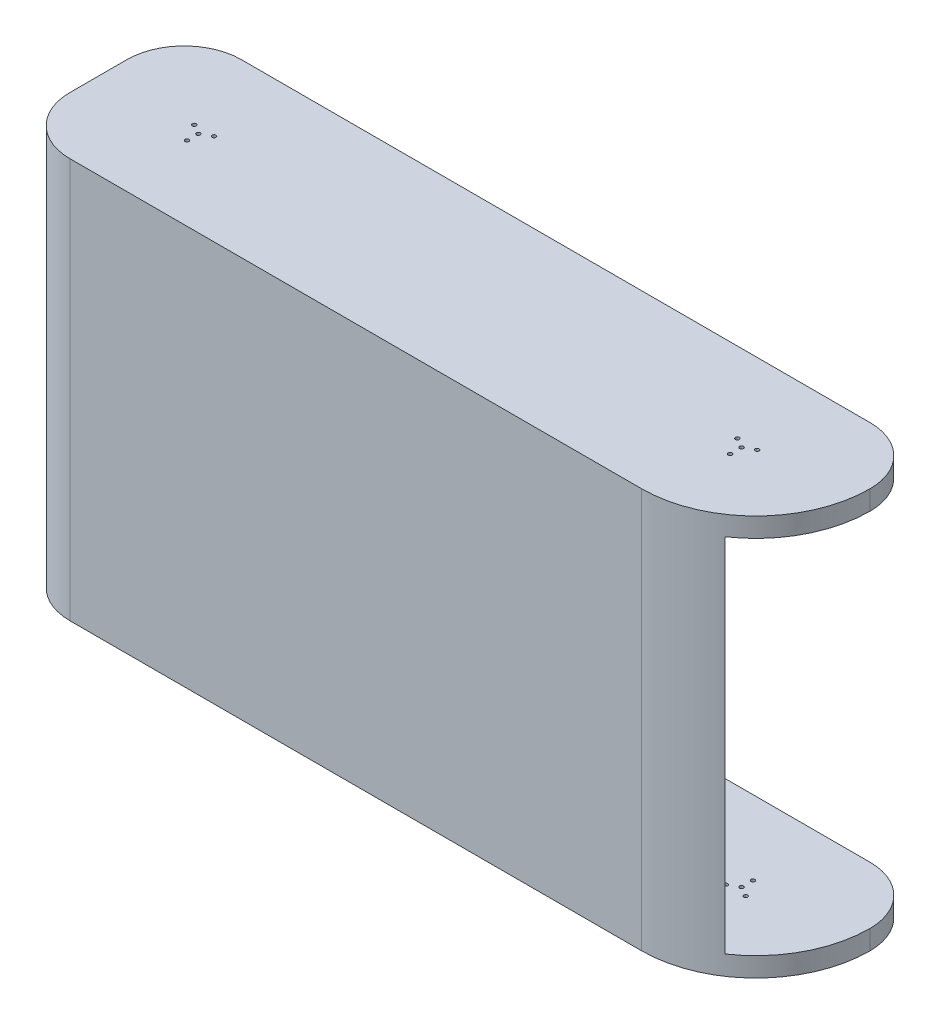
SolidWorks part; units mm, degrees
ref_plane "Front Plane" through (0, 0, 0) normal (1, 0, 0) x (0, 1, 0)
ref_plane "Top Plane" through (0, 0, 0) normal (0, 0, 1) x (0, 1, 0)
ref_plane "Right Plane" through (0, 0, 0) normal (0, 1, 0) x (-1, 0, 0)
sketch "Sketch1" plane through (0, 0, 0) normal (0, 1, 0) x (-1, 0, 0)
  line L1 (650, -150) -> (-650, -150)
  line L2 (650, -150) -> (650, 150)
  line L3 (650, 150) -> (-650, 150)
  line L4 (-650, -150) -> (-650, 150)
  line L5 (650, -150) -> (-650, 150) construction
  line L6 (650, 150) -> (-650, -150) construction
  point P0 (0, 0)
  dimension "D1" = 300
  dimension "D2" = 1300
extrude "Boss-Extrude1" add sketch "Sketch1" along normal blind 700
fillet "Fillet1" radius 200 1 edges at (650, 350, 150)
fillet "Fillet2" radius 100 1 edges at (650, 350, -150)
fillet "Fillet3" radius 100 1 edges at (-650, 350, 150)
fillet "Fillet4" radius 100 1 edges at (-650, 350, -150)
sketch "Sketch3" plane through (0, 0, 0) normal (0, -1, 0) x (1, 0, 0)
  line L0 (475, 0) -> (475, -20) construction
  line L1 (475, 0) -> (457.6795, 10) construction
  line L2 (475, 0) -> (492.3205, 10) construction
  line L3 (475, 0) -> (-475, 0) construction
  line L4 (-475, 0) -> (-475, -20) construction
  line L5 (-475, 0) -> (-492.3205, 10) construction
  line L6 (-475, 0) -> (-457.6795, 10) construction
  circle A1 centre (475, 0) radius 3.4
  circle A2 centre (492.3205, 10) radius 3.4
  circle A3 centre (457.6795, 10) radius 3.4
  circle A4 centre (475, -20) radius 3.4
  circle A5 centre (475, 0) radius 57.2068 construction
  circle A6 centre (-475, 0) radius 57.2068 construction
  circle A7 centre (-475, 0) radius 3.4
  circle A8 centre (-457.6795, 10) radius 3.4
  circle A9 centre (-492.3205, 10) radius 3.4
  circle A10 centre (-475, -20) radius 3.4
  dimension "D4" = 6.8
  dimension "D10" = 6.8
  dimension "D1" = 120
  dimension "D2" = 120
  dimension "D3" = 20
  dimension "D5" = 475
  dimension "D6" = 475
  dimension "D7" = 20
  dimension "D8" = 120
  dimension "D9" = 120
extrude "Cut-Extrude1" cut sketch "Sketch3" against normal blind 100
sketch "Sketch4" plane through (0, 700, 0) normal (0, 1, 0) x (-1, 0, 0)
  line L0 (-475, 0) -> (-475, 20) construction
  line L1 (-475, 0) -> (-492.3205, -10) construction
  line L2 (-475, 0) -> (-457.6795, -10) construction
  line L3 (475, 0) -> (475, 20) construction
  line L4 (475, 0) -> (457.6795, -10) construction
  line L5 (475, 0) -> (492.3205, -10) construction
  circle A2 centre (-475, 0) radius 3.4
  circle A3 centre (-475, 20) radius 3.4
  circle A4 centre (-492.3205, -10) radius 3.4
  circle A5 centre (-457.6795, -10) radius 3.4
  circle A6 centre (475, 0) radius 3.4
  circle A7 centre (475, 20) radius 3.4
  circle A8 centre (457.6795, -10) radius 3.4
  circle A9 centre (492.3205, -10) radius 3.4
  dimension "D4" = 6.8
  dimension "D8" = 6.8
  dimension "D1" = 20
  dimension "D2" = 120
  dimension "D3" = 120
  dimension "D5" = 20
  dimension "D6" = 120
  dimension "D7" = 120
extrude "Cut-Extrude2" cut sketch "Sketch4" against normal blind 100
sketch "Sketch5" plane through (-650, 0, 0) normal (-1, 0, 0) x (0, -1, 0)
  line L0 (-350, 150) -> (-350, -218.4002) construction
  line L1 (-700, 150) -> (0, 150) construction
  line L2 (-665.9881, 115.8313) -> (-34.0119, 115.8313)
  line L3 (-665.9881, 115.8313) -> (-665.9881, -203.7498)
  line L4 (-665.9881, -203.7498) -> (-34.0119, -203.7498)
  line L5 (-34.0119, 115.8313) -> (-34.0119, -203.7498)
extrude "Cut-Extrude4" cut sketch "Sketch5" against normal blind 1410
sketch "Sketch6" plane through (0, 34.0119, 0) normal (0, 1, 0) x (-1, 0, 0)
  line L0 (-550, -150) -> (550, -150) construction
  line L1 (-149.5431, -150) -> (203.1529, -150)
  line L2 (-149.5431, -150) -> (-149.5431, -114.9789)
  line L3 (-149.5431, -114.9789) -> (203.1529, -114.9789)
  line L4 (203.1529, -150) -> (203.1529, -114.9789)
extrude "Boss-Extrude2" add sketch "Sketch6" along normal up to surface (631.9761 mm away) up to face at (-99.8244, 665.9881, -20.9309)
